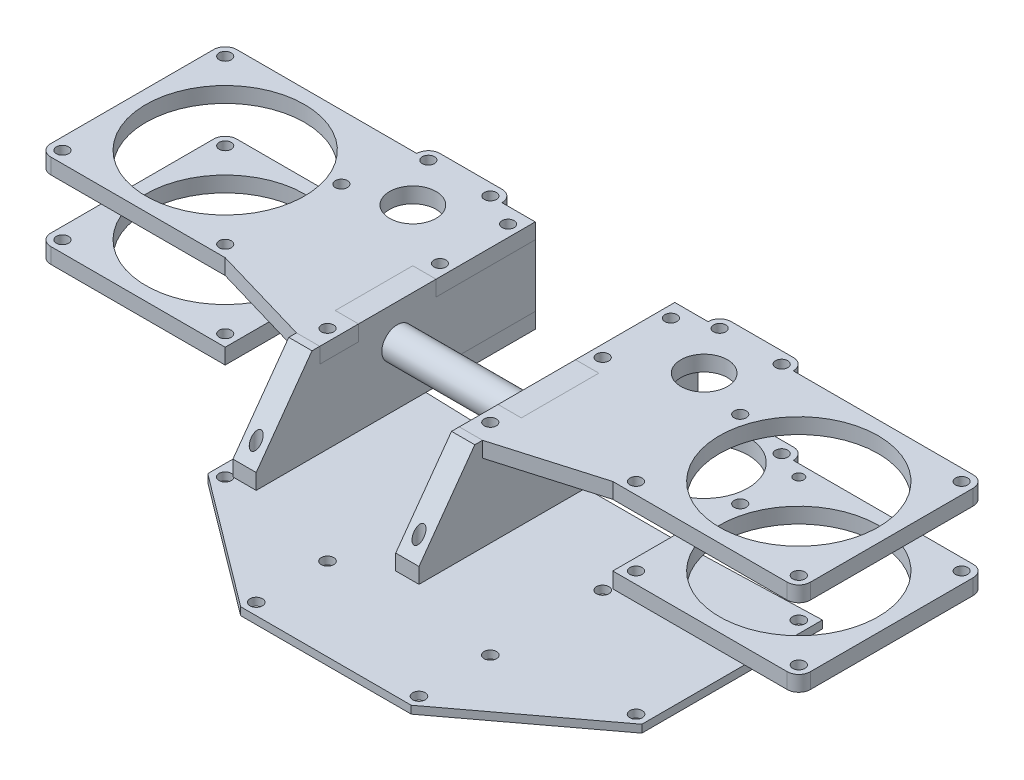
SolidWorks part; units mm, degrees
material "Alum Plate"
ref_plane "Front Plane" through (0, 0, 0) normal (0, 0, 1) x (1, 0, 0)
ref_plane "Top Plane" through (0, 0, 0) normal (0, 1, 0) x (1, 0, 0)
ref_plane "Right Plane" through (0, 0, 0) normal (1, 0, 0) x (0, 0, -1)
sketch "Sketch1" plane through (0, 0, 0) normal (0, 1, 0) x (1, 0, 0)
  line L0 (0, 0) -> (117.475, 0) construction
  line L1 (-117.475, 0) -> (0, 0) construction
  line L3 (-9.525, 197.485) -> (-3.175, 197.485)
  line L4 (-9.525, 197.485) -> (-9.525, 70.485)
  line L5 (-9.525, 70.485) -> (-3.175, 70.485)
  line L6 (-3.175, 197.485) -> (-3.175, 70.485)
  line L7 (-9.525, 197.485) -> (-3.175, 70.485) construction
  line L8 (-9.525, 70.485) -> (-3.175, 197.485) construction
  line L14 (-155.575, -76.2) -> (155.575, -76.2)
  line L20 (-28.575, 38.1) -> (0, 38.1) construction
  line L21 (-6.35, 133.985) -> (0, 133.985)
  line L29 (0, 0) -> (0, -18.415) construction
  line L30 (-117.475, 0) -> (-59.6589, 19.05) construction
  line L43 (59.6589, 19.05) -> (117.475, 0) construction
  line L44 (-86.6074, 10.1707) -> (-86.2044, 10.3034)
  line L55 (-77.1578, 13.2842) -> (-76.7548, 13.417)
  line L69 (-155.575, -76.2) -> (-155.575, 38.1)
  line L70 (-155.575, 38.1) -> (155.575, 38.1)
  line L71 (155.575, -76.2) -> (155.575, 38.1)
  line L78 (0, 133.985) -> (0, -18.415)
  line L79 (0, -18.415) -> (0, -170.815) construction
  line L80 (-9.525, -234.315) -> (-3.175, -234.315) construction
  line L81 (-9.525, -234.315) -> (-9.525, -107.315) construction
  line L82 (-9.525, -107.315) -> (-3.175, -107.315) construction
  line L83 (-3.175, -234.315) -> (-3.175, -107.315) construction
  line L84 (-9.525, -234.315) -> (-3.175, -107.315) construction
  line L85 (-9.525, -107.315) -> (-3.175, -234.315) construction
  line L86 (0, -170.815) -> (-6.35, -170.815) construction
  line L87 (-38.1, -76.2) -> (-28.575, -76.2)
  line L88 (-38.1, -76.2) -> (-38.1, 38.1)
  line L89 (-38.1, 38.1) -> (-28.575, 38.1)
  line L90 (-28.575, -76.2) -> (-28.575, 38.1)
  line L91 (38.1, -76.2) -> (28.575, -76.2)
  line L92 (38.1, -76.2) -> (38.1, 38.1)
  line L93 (38.1, 38.1) -> (28.575, 38.1)
  line L94 (28.575, -76.2) -> (28.575, 38.1)
  line L95 (0, 38.1) -> (28.575, 38.1) construction
  circle A0 centre (-117.475, 0) radius 32.5
  circle A1 centre (-117.475, 0) radius 25
  circle A2 centre (117.475, 0) radius 32.5
  circle A3 centre (117.475, 0) radius 25
  circle A4 centre (-59.6589, 19.05) radius 18
  circle A5 centre (59.6589, 19.05) radius 18
  circle A8 centre (-81.6811, 11.7938) radius 4.7625
  point P8 (-6.35, 133.985)
  point P21 (117.475, 32.5)
  point P25 (59.6589, 37.05)
  point P29 (59.6589, 1.05)
  point P31 (0, -76.2)
  point P32 (-6.35, -170.815)
  point P62 (149.975, 0)
  dimension "D1" = 50
  dimension "D2" = 65
  dimension "D8" = 36
  dimension "D11" = 152.4
  dimension "D12" = 56.515
  dimension "D16" = 9.525
  dimension "D3" = 127
  dimension "D4" = 6.35
  dimension "D5" = 234.95
  dimension "D6" = 38.1
  dimension "D7" = 38.1
  dimension "D9" = 114.3
  dimension "D10" = 9.525
  dimension "D13" = 9.525
  dimension "D14" = 57.15
  dimension "D15" = 60.8736
  dimension "D18" = 19.05
sketch "Sketch2" plane through (0, 0, 0) normal (1, 0, 0) x (0, 0, -1)
  line L0 (0, 25.4) -> (0, 56.175) construction
  line L1 (-32.5, 59.675) -> (32.5, 59.675)
  line L2 (-32.5, 59.675) -> (-32.5, 52.675)
  line L3 (-32.5, 52.675) -> (32.5, 52.675)
  line L4 (32.5, 59.675) -> (32.5, 52.675)
  line L5 (-32.5, 59.675) -> (32.5, 52.675) construction
  line L6 (-32.5, 52.675) -> (32.5, 59.675) construction
  line L7 (-32.5, 88.9) -> (32.5, 88.9)
  line L8 (-32.5, 88.9) -> (-32.5, 81.9)
  line L9 (-32.5, 81.9) -> (32.5, 81.9)
  line L10 (32.5, 88.9) -> (32.5, 81.9)
  line L11 (-32.5, 88.9) -> (32.5, 81.9) construction
  line L12 (-32.5, 81.9) -> (32.5, 88.9) construction
  line L13 (-25.8191, 0) -> (33.9817, 0) construction
  line L14 (-18.415, 76.2) -> (-170.815, 76.2)
  line L15 (-76.2, 90.775) -> (38.1, 90.775)
  line L16 (-76.2, 90.775) -> (-76.2, 52.675)
  line L17 (-76.2, 52.675) -> (38.1, 52.675)
  line L18 (38.1, 90.775) -> (38.1, 52.675)
  line L19 (-5.8284, 26.8817) -> (0.4649, 73.66)
  line L20 (-18.415, 28.575) -> (-18.415, 76.2) construction
  line L21 (133.985, 0) -> (-18.415, 0) construction
  line L22 (-76.2, 84.425) -> (38.1, 84.425)
  line L23 (-76.2, 59.025) -> (38.1, 59.025)
  line L24 (-31.0016, 26.8817) -> (-37.2949, 73.66)
  line L25 (-18.415, 28.575) -> (-24.765, 64.8535) construction
  line L26 (-18.415, 76.2) -> (133.985, 76.2)
  line L32 (-76.2, 8.225) -> (38.1, 8.225)
  line L33 (-76.2, 8.225) -> (-76.2, 5.05)
  line L38 (-76.2, 5.05) -> (38.1, 5.05)
  line L39 (38.1, 8.225) -> (38.1, 5.05)
  line L40 (1.05, 39.9242) -> (37.05, 39.9242)
  line L41 (1.05, 39.9242) -> (1.05, 84.425)
  line L42 (1.05, 84.425) -> (37.05, 84.425)
  line L43 (37.05, 39.9242) -> (37.05, 84.425)
  line L44 (1.05, 39.9242) -> (37.05, 84.425) construction
  line L45 (1.05, 84.425) -> (37.05, 39.9242) construction
  line L46 (-38.1, 90.775) -> (-38.1, 52.675)
  line L47 (-38.1, 71.725) -> (0, 71.725) construction
  line L48 (0, 71.725) -> (38.1, 71.725) construction
  line L49 (-76.2, 8.225) -> (38.1, 5.05) construction
  line L50 (-76.2, 5.05) -> (38.1, 8.225) construction
  circle A0 centre (0, 25.4) radius 25.4
  circle A3 centre (-170.815, 76.2) radius 63.5
  circle A4 centre (-18.415, 76.2) radius 6.35
  circle A5 centre (-18.415, 28.575) radius 18
  circle A6 centre (133.985, 76.2) radius 63.5
  circle A7 centre (-18.415, 76.2) radius 19.05
  circle A8 centre (-18.415, 28.575) radius 12.7
  circle A9 centre (-24.765, 64.8535) radius 17.5006
  point P2 (0, 56.175)
  point P8 (0, 85.4)
  point P16 (-0.415, 28.575)
  point P28 (-36.415, 28.575)
  point P32 (19.05, 62.1746)
  point P34 (-234.315, 76.2)
  point P47 (0, 50.8)
  point P57 (-19.05, 6.6375)
  dimension "D1" = 50.8
  dimension "D8" = 38.1
  dimension "D2" = 25.4
  dimension "D11" = 12.7
  dimension "D12" = 36
  dimension "D14" = 35.0012
  dimension "D17" = 36.83
  dimension "D3" = 7
  dimension "D4" = 38.1
  dimension "D5" = 22.225
  dimension "D6" = 6.35
  dimension "D7" = 6.35
  dimension "D9" = 76.2
  dimension "D10" = 44.5008
  dimension "D13" = 47.625
  dimension "D15" = 3.175
  dimension "D16" = 25.4
  dimension "D18" = 44.45
  dimension "D19" = 6.35
sketch "Sketch5" plane through (0, 0, 0) normal (0, 1, 0) x (1, 0, 0)
  line L0 (-100.076, -18.415) -> (-28.575, -18.415) construction
  line L1 (-100.076, -4.415) -> (-68.58, -4.415)
  line L2 (-100.076, -4.415) -> (-100.076, -32.415)
  line L3 (-100.076, -32.415) -> (-68.58, -32.415)
  line L4 (-68.58, -4.415) -> (-68.58, -32.415)
  line L5 (-100.076, -4.415) -> (-68.58, -32.415) construction
  line L6 (-100.076, -32.415) -> (-68.58, -4.415) construction
  line L11 (-28.575, -76.2) -> (-28.575, 38.1) construction
  line L13 (-68.58, -0.415) -> (-28.575, -0.415)
  line L14 (-68.58, -0.415) -> (-68.58, -36.415)
  line L15 (-68.58, -36.415) -> (-28.575, -36.415)
  line L16 (-28.575, -0.415) -> (-28.575, -36.415)
  line L17 (-68.58, -0.415) -> (-28.575, -36.415) construction
  line L18 (-68.58, -36.415) -> (-28.575, -0.415) construction
  point P0 (-84.328, -18.415)
  point P5 (-111.4721, -67.34)
  point P6 (-25.4, -35.34)
  point P10 (-48.5775, -18.415)
  dimension "D1" = 40.005
  dimension "D2" = 31.496
  dimension "D3" = 28
ref_plane "Plane1" through (0, 84.425, 0) normal (0, 1, 0) x (1, 0, 0)
ref_plane "Plane2" through (0, 59.025, 0) normal (0, -1, 0) x (-1, 0, 0)
ref_plane "Plane3" through (28.575, 0, 0) normal (1, 0, 0) x (0, 0, -1)
sketch "Sketch6" plane through (28.575, 0, 0) normal (1, 0, 0) x (0, 0, -1)
  line L0 (-18.415, 90.775) -> (-18.415, 76.2) construction
  line L2 (-76.2, 59.025) -> (-53.34, 90.775)
  line L3 (-76.2, 90.775) -> (38.1, 90.775) construction
  line L4 (-53.34, 90.775) -> (-50.165, 90.775)
  line L5 (-50.165, 90.775) -> (-50.165, 84.425)
  line L6 (-76.2, 84.425) -> (38.1, 84.425) construction
  line L7 (-50.165, 84.425) -> (-34.29, 84.425)
  line L8 (-2.54, 59.025) -> (-2.54, 52.675)
  line L10 (-32.5, 52.675) -> (32.5, 52.675) construction
  line L11 (-76.2, 52.675) -> (-76.2, 59.025)
  line L12 (-76.2, 52.675) -> (-2.54, 52.675)
  line L13 (-34.29, 84.425) -> (-34.29, 90.775)
  line L14 (-34.29, 90.775) -> (-2.54, 90.775)
  line L15 (-2.54, 84.425) -> (-2.54, 90.775)
  line L16 (-34.29, 84.425) -> (-2.54, 90.775) construction
  line L17 (-34.29, 90.775) -> (-2.54, 84.425) construction
  line L19 (-76.2, 59.025) -> (38.1, 59.025) construction
  line L20 (-2.54, 59.025) -> (38.1, 59.025)
  line L21 (-2.54, 59.025) -> (-2.54, 84.425) construction
  line L22 (-2.54, 84.425) -> (38.1, 84.425)
  line L23 (38.1, 59.025) -> (38.1, 84.425)
  line L24 (-2.54, 59.025) -> (38.1, 84.425) construction
  line L25 (-2.54, 84.425) -> (38.1, 59.025) construction
  line L26 (-2.54, 84.425) -> (-2.54, 59.025) construction
  point P1 (-76.2, 34.0828)
  point P2 (0, 0)
  point P4 (-72.6489, 67.9657)
  point P5 (-76.2, 52.675)
  point P10 (-18.415, 87.6)
  point P22 (-34.29, 82.3754)
  point P26 (-76.2, 59.025)
  point P27 (-4.5781, 52.675)
  point P28 (17.78, 71.725)
  point P36 (0.7165, 84.425)
  point P37 (-1.9308, 84.425)
  dimension "D2" = 31.75
  dimension "D3" = 3.175
  dimension "D4" = 31.75
extrude "Boss-Extrude1" add sketch "Sketch6" along normal up to vertex (9.525 mm away) up to point (38.1, 0, -38.1)
sketch "Sketch7" plane through (0, 84.425, 0) normal (0, 1, 0) x (1, 0, 0)
  line L0 (28.575, -50.165) -> (38.1, -50.165)
  line L2 (155.575, -76.2) -> (155.575, 38.1) construction
  line L3 (155.575, -38.1) -> (155.575, 38.1)
  line L4 (155.575, 38.1) -> (28.575, 38.1)
  line L5 (28.575, 38.1) -> (28.575, -2.54)
  line L6 (155.575, -38.1) -> (79.375, -38.1)
  line L7 (79.375, -38.1) -> (38.1, -50.165)
  line L8 (117.475, 38.1) -> (117.475, 0) construction
  line L9 (117.475, 0) -> (117.475, -38.1) construction
  line L10 (28.575, -34.29) -> (38.1, -34.29)
  line L11 (38.1, -34.29) -> (38.1, -2.54)
  line L12 (38.1, -2.54) -> (28.575, -2.54)
  line L13 (28.575, -76.2) -> (28.575, 38.1) construction
  line L14 (28.575, -34.29) -> (28.575, -50.165)
  circle A0 centre (117.475, 0) radius 32.5 construction
  circle A1 centre (117.475, 0) radius 32.5
  circle A3 centre (59.6589, 19.05) radius 9.525
  point P20 (28.575, -2.54)
  dimension "D2" = 19.05
extrude "Boss-Extrude2" add sketch "Sketch7" along normal up to surface (6.35 mm away) separate body up to face at (33.3375, 90.775, 51.7525)
sketch "Sketch8" plane through (0, 59.025, 0) normal (0, -1, 0) x (-1, 0, 0)
  line L1 (-79.375, -38.1) -> (-155.575, -38.1)
  line L2 (-79.375, -38.1) -> (-79.375, 38.1) construction
  line L3 (-79.375, 38.1) -> (-155.575, 38.1)
  line L4 (-155.575, -38.1) -> (-155.575, 38.1)
  line L5 (-79.375, -38.1) -> (-155.575, 38.1) construction
  line L6 (-79.375, 38.1) -> (-155.575, -38.1) construction
  line L7 (155.575, 38.1) -> (-155.575, 38.1) construction
  line L8 (-28.575, 38.1) -> (-79.375, 38.1)
  line L12 (-79.375, -38.1) -> (-79.375, -3.175)
  line L13 (-79.375, -3.175) -> (-38.1, -3.175)
  line L14 (-38.1, -76.2) -> (-38.1, 38.1) construction
  line L15 (-38.1, -3.175) -> (-38.1, -2.54)
  line L16 (-38.1, -2.54) -> (-28.575, -2.54)
  line L17 (-28.575, -2.54) -> (-28.575, 38.1)
  circle A0 centre (-117.475, 0) radius 32.5 construction
  circle A1 centre (-117.475, 0) radius 32.5
  circle A3 centre (-59.6589, 19.05) radius 18
  circle A4 centre (-59.6589, 19.05) radius 18 construction
  dimension "D1" = 22.225
extrude "Boss-Extrude3" add sketch "Sketch8" along normal up to vertex (6.35 mm away) separate body up to point (0, 52.675, -38.1)
sketch "Sketch14" plane through (0, 59.025, 0) normal (0, 1, 0) x (1, 0, 0)
  line L0 (59.6589, 38.1) -> (59.6589, 19.05) construction
  line L1 (72.3589, 42.8625) -> (46.9589, 42.8625)
  line L2 (28.575, 38.1) -> (155.575, 38.1) construction
  line L3 (67.5964, 38.1) -> (51.7214, 38.1)
  arc A0 (67.5964, 38.1) -> (72.3589, 42.8625) centre (72.3589, 38.1) ccw
  arc A1 (46.9589, 42.8625) -> (51.7214, 38.1) centre (46.9589, 38.1) ccw
  dimension "D1" = 9.525
  dimension "D2" = 25.4
extrude "Boss-Extrude4" add sketch "Sketch14" against normal up to surface (6.35 mm away) up to face at (117.475, 52.675, -32.5)
extrude "Boss-Extrude5" add sketch "Sketch14<2>" against normal up to surface (-25.4 mm away) from surface up to face at (61.9125, 84.425, 17.399) starting at face at (59.6589, 90.775, -28.575)
sketch "Sketch14<2>" plane through (0, 59.025, 0) normal (0, 1, 0) x (1, 0, 0) same geometry as "Sketch14"
sketch "Sketch15" plane through (0, 52.675, 0) normal (0, -1, 0) x (1, 0, 0)
  line L0 (-81.6811, -11.7938) -> (81.6811, -11.7938) construction
  line L1 (59.6589, -19.05) -> (117.475, 0) construction
  line L2 (79.375, 38.1) -> (79.375, 3.175) construction
  line L3 (155.575, 38.1) -> (79.375, 38.1) construction
  line L4 (155.575, 76.2) -> (155.575, -38.1) construction
  line L5 (-155.575, -38.1) -> (155.575, -38.1) construction
  line L6 (150.8125, 38.1) -> (155.575, 38.1)
  line L7 (155.575, 38.1) -> (155.575, 33.3375)
  line L8 (150.8125, -38.1) -> (155.575, -38.1)
  line L9 (155.575, -38.1) -> (155.575, -33.3375)
  line L10 (33.3375, -38.1) -> (33.3375, -31.75) construction
  line L11 (33.3375, -31.75) -> (33.3375, -3.81) construction
  line L12 (33.3375, -3.81) -> (33.3375, 2.54) construction
  line L13 (38.1, 2.54) -> (28.575, 2.54) construction
  line L14 (33.3375, 2.54) -> (33.3375, -3.81) construction
  line L15 (33.3375, 34.29) -> (33.3375, 42.2275) construction
  line L16 (33.3375, 42.2275) -> (33.3375, 50.165) construction
  line L17 (38.1, 50.165) -> (28.575, 50.165) construction
  line L18 (38.1, 34.29) -> (28.575, 34.29) construction
  line L19 (38.1, 2.54) -> (28.575, 2.54) construction
  line L20 (33.3375, 2.54) -> (33.3375, -3.81) construction
  circle A0 centre (46.9589, -38.1) radius 2.4892
  circle A1 centre (72.3589, -38.1) radius 2.4892
  circle A3 centre (81.6811, -11.7938) radius 2.4892
  circle A4 centre (150.8125, -33.3375) radius 2.4892
  circle A5 centre (150.8125, 33.3375) radius 2.4892
  circle A6 centre (84.1375, 33.3375) radius 2.4892
  circle A7 centre (84.1375, 33.3375) radius 4.7625 construction
  arc A8 (155.575, 33.3375) -> (150.8125, 38.1) centre (150.8125, 33.3375) ccw
  arc A9 (150.8125, -38.1) -> (155.575, -33.3375) centre (150.8125, -33.3375) ccw
  arc A10 (155.575, -33.3375) -> (150.8125, -38.1) centre (150.8125, -33.3375) ccw construction
  arc A11 (150.8125, 38.1) -> (155.575, 33.3375) centre (150.8125, 33.3375) ccw construction
  circle A12 centre (33.3375, -31.75) radius 2.4892
  circle A14 centre (33.3375, -3.81) radius 2.4892
  circle A15 centre (33.3375, 42.2275) radius 2.4892
  dimension "D1" = 4.9784
  dimension "D2" = 9.525
  dimension "D3" = 6.35
  dimension "D4" = 6.35
extrude "Cut-Extrude9" cut sketch "Sketch15" against normal through all
sketch "Sketch16" plane through (28.575, 0, 0) normal (-1, 0, 0) x (0, 0, 1)
  circle A0 centre (18.415, 76.2) radius 6.35 construction
  circle A1 centre (18.415, 76.2) radius 6.35
extrude "Cut-Extrude10" cut sketch "Sketch16" against normal up to next (9.525 mm away)
sketch "Sketch19" plane through (0, 52.675, 0) normal (0, -1, 0) x (1, 0, 0)
  line L0 (33.3375, 76.2) -> (33.3375, 71.4375) construction
  line L1 (38.1, 76.2) -> (28.575, 76.2) construction
  line L2 (33.3375, 71.4375) -> (38.1, 71.4375) construction
  line L3 (38.1, 76.2) -> (38.1, 2.54) construction
  circle A0 centre (33.3375, -3.81) radius 2.0193
  circle A1 centre (33.3375, -31.75) radius 2.0193
  circle A2 centre (33.3375, 42.2275) radius 2.0193
  circle A3 centre (33.3375, 71.4375) radius 2.0193
  circle A4 centre (33.3375, 42.2275) radius 2.4892 construction
  dimension "D1" = 4.0386
extrude "Cut-Extrude11" cut sketch "Sketch19" against normal through all
sketch "Sketch22" plane through (0, 52.675, 0) normal (0, -1, 0) x (1, 0, 0)
  line L0 (150.8125, -33.3375) -> (84.1375, -33.3375) construction
  line L1 (84.1375, -33.3375) -> (84.1375, 33.3375) construction
  circle A0 centre (84.1375, -33.3375) radius 2.0193
  circle A1 centre (33.3375, -31.75) radius 2.0193 construction
extrude "Cut-Extrude12" cut sketch "Sketch22" against normal up to next (6.35 mm away)
mirror "Mirror2" about plane through (0, 0, 0) normal (1, 0, 0) of bodies 139 122 141 106 108 111
sketch "Sketch17" plane through (38.1, 0, 0) normal (1, 0, 0) x (0, 0, -1)
  circle A0 centre (-18.415, 76.2) radius 6.35 construction
  circle A1 centre (-18.415, 76.2) radius 6.35
extrude "Boss-Extrude6" add sketch "Sketch17" against normal up to surface (76.2 mm away) separate body up to face at (-38.1, 76.2, 24.765)
ref_plane "Plane4" through (0, 8.225, 0) normal (0, -1, 0) x (-1, 0, 0)
sketch "Sketch21" plane through (0, 8.225, 0) normal (0, -1, 0) x (-1, 0, 0)
  line L0 (-84.1375, -33.3375) -> (-84.1375, 33.3375) construction
  line L1 (-84.1375, 33.3375) -> (-33.3375, 31.75) construction
  line L2 (-33.3375, 31.75) -> (33.3375, 31.75) construction
  line L3 (33.3375, 31.75) -> (84.1375, 33.3375) construction
  line L4 (84.1375, 33.3375) -> (84.1375, -33.3375) construction
  line L5 (84.1375, -33.3375) -> (33.3375, -71.4375) construction
  line L6 (33.3375, -71.4375) -> (-33.3375, -71.4375) construction
  line L7 (-33.3375, -71.4375) -> (-84.1375, -33.3375) construction
  line L8 (-88.9, -35.7188) -> (-88.9, 38.2512)
  line L9 (-88.9, 38.2512) -> (-33.2631, 36.5125)
  line L10 (-33.2631, 36.5125) -> (33.2631, 36.5125)
  line L11 (33.2631, 36.5125) -> (88.9, 38.2512)
  line L12 (88.9, 38.2512) -> (88.9, -35.7188)
  line L13 (88.9, -35.7188) -> (34.925, -76.2)
  line L14 (34.925, -76.2) -> (-34.925, -76.2)
  line L15 (-34.925, -76.2) -> (-88.9, -35.7188)
  circle A0 centre (-84.1375, 33.3375) radius 2.5527
  circle A1 centre (-84.1375, -33.3375) radius 2.5527
  circle A2 centre (-33.3375, 31.75) radius 2.5527
  circle A3 centre (-33.3375, 3.81) radius 2.5527
  circle A4 centre (-33.3375, -42.2275) radius 2.5527
  circle A5 centre (-33.3375, -71.4375) radius 2.5527
  circle A6 centre (33.3375, -71.4375) radius 2.5527
  circle A7 centre (33.3375, -42.2275) radius 2.5527
  circle A8 centre (33.3375, 3.81) radius 2.5527
  circle A9 centre (33.3375, 31.75) radius 2.5527
  circle A10 centre (84.1375, 33.3375) radius 2.5527
  circle A11 centre (84.1375, -33.3375) radius 2.5527
  point P44 (-84.1375, 33.3375)
  point P46 (84.1375, 33.3375)
  dimension "D1" = 5.1054
  dimension "D2" = 4.7625
extrude "Boss-Extrude7" add sketch "Sketch21" along normal up to vertex (3.175 mm away) separate body up to point (0, 5.05, -38.1)
